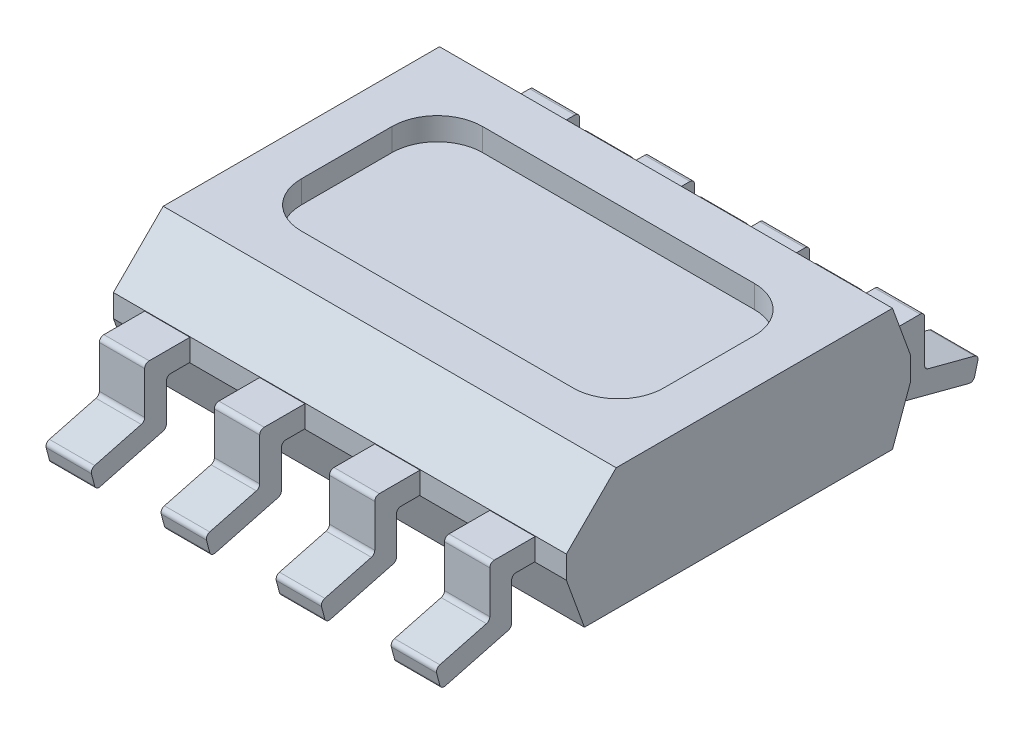
SolidWorks part; units mm, degrees
ref_plane "Front Plane" through (0, 0, 0) normal (0, 0, 1) x (1, 0, 0)
ref_plane "Top Plane" through (0, 0, 0) normal (0, 1, 0) x (1, 0, 0)
ref_plane "Right Plane" through (0, 0, 0) normal (1, 0, 0) x (0, 0, -1)
sketch "Sketch1" plane through (0, 0, 0) normal (0, 1, 0) x (1, 0, 0)
  line L1 (0, 0) -> (5, 0)
  line L2 (0, 0) -> (0, 3.8)
  line L3 (0, 3.8) -> (5, 3.8)
  line L4 (5, 0) -> (5, 3.8)
  dimension "D1" = 5
  dimension "D2" = 3.8
extrude "Boss-Extrude1" add sketch "Sketch1" along normal blind 1.35
sketch "Sketch2" plane through (5, 0, 0) normal (1, 0, 0) x (0, 0, -1)
  line L0 (0.55, 1.35) -> (0, 0.8)
  line L1 (0, 1.35) -> (3.8, 1.35) construction
  line L2 (0, 1.35) -> (0, 0) construction
  line L3 (0, 0.8) -> (0, 0.55)
  line L4 (0, 0.55) -> (0.2, 0)
  line L5 (0, 0) -> (3.8, 0) construction
  line L6 (0.2, 0) -> (3.6, 0)
  line L7 (3.6, 0) -> (3.8, 0.55)
  line L8 (3.8, 1.35) -> (3.8, 0) construction
  line L9 (3.8, 0.55) -> (3.8, 0.8)
  line L10 (3.8, 0.8) -> (3.6, 1.35)
  line L11 (3.6, 1.35) -> (0.55, 1.35)
  line M9 (0, 0) -> (3.8, 0)
  line M10 (3.8, 0) -> (3.8, 1.35)
  line M11 (3.8, 1.35) -> (0, 1.35)
  line M12 (0, 1.35) -> (0, 0)
  dimension "D1" = 0.55
  dimension "D2" = 0.25
  dimension "D3" = 0.25
  dimension "D4" = 0.55
  dimension "D5" = 0.55
  dimension "D6" = 0.55
  dimension "D7" = 0.2
  dimension "D8" = 0.2
  dimension "D9" = 0.2
extrude "Cut-Extrude1" cut sketch "Sketch2" against normal blind 5 contours L0 M11 M12 | L4 M12 M9 | L7 M9 M10 | L10 M10 M11 region at (5, 1.1667, -0.1833) region at (5, 1.1667, -3.7333) region at (5, 0.1833, -0.0667) region at (5, 0.1833, -3.7333)
sketch "Sketch3" plane through (0, 1.35, 0) normal (0, 1, 0) x (1, 0, 0)
  line L0 (0, 3.6) -> (0, 0.55) construction
  line L1 (1, 3.075) -> (4, 3.075)
  line L2 (0.5, 2.575) -> (0.5, 1.575)
  line L3 (1, 1.075) -> (4, 1.075)
  line L4 (4.5, 2.575) -> (4.5, 1.575)
  line L5 (0, 3.6) -> (5, 3.6) construction
  line L7 (0, 0.55) -> (5, 0.55) construction
  arc A0 (0.5, 1.575) -> (1, 1.075) centre (1, 1.575) ccw
  arc A1 (4, 1.075) -> (4.5, 1.575) centre (4, 1.575) ccw
  arc A2 (4, 3.075) -> (4.5, 2.575) centre (4, 2.575) cw
  arc A3 (0.5, 2.575) -> (1, 3.075) centre (1, 2.575) cw
  point P14 (4.5, 1.075)
  point P17 (4.5, 3.075)
  point P20 (0.5, 3.075)
  dimension "D6" = 0.5
  dimension "D1" = 4
  dimension "D2" = 2
  dimension "D3" = 0.5
  dimension "D4" = 0.525
  dimension "D5" = 0.525
extrude "Cut-Extrude2" cut sketch "Sketch3" against normal blind 0.25
ref_plane "Plane1" through (4.405, 0, 0) normal (1, 0, 0) x (0, 0, -1)
sketch "Sketch4" plane through (4.405, 0, 0) normal (1, 0, 0) x (0, 0, -1)
  line L0 (3.8, 0.795) -> (4.25, 0.795)
  line L1 (3.8, 0.8) -> (3.8, 0.55) construction
  line L2 (4.3, 0.745) -> (4.3, 0.2786)
  line L3 (4.3373, 0.2302) -> (4.8516, 0.0948)
  line L4 (4.8873, 0.0337) -> (4.8516, -0.1016)
  line L5 (4.7906, -0.1373) -> (4.0973, 0.0452)
  line L6 (4.06, 0.0935) -> (4.06, 0.505)
  line L7 (4.01, 0.555) -> (3.8, 0.555)
  line L8 (3.8, 0.555) -> (3.8, 0.795)
  arc A0 (4.8516, -0.1016) -> (4.7906, -0.1373) centre (4.8033, -0.0889) cw
  arc A1 (4.8516, 0.0948) -> (4.8873, 0.0337) centre (4.8389, 0.0465) cw
  arc A2 (4.0973, 0.0452) -> (4.06, 0.0935) centre (4.11, 0.0935) cw
  arc A3 (4.3, 0.2786) -> (4.3373, 0.2302) centre (4.35, 0.2786) ccw
  arc A4 (4.06, 0.505) -> (4.01, 0.555) centre (4.01, 0.505) ccw
  arc A5 (4.25, 0.795) -> (4.3, 0.745) centre (4.25, 0.745) cw
  point P17 (4.8389, -0.15)
  point P20 (4.9, 0.0821)
  point P23 (4.06, 0.055)
  point P28 (4.06, 0.555)
  point P31 (4.3, 0.795)
  dimension "D9" = 0.05
  dimension "D1" = 1.1
  dimension "D2" = 0.15
  dimension "D3" = 0.24
  dimension "D4" = 0.24
  dimension "D5" = 0.24
  dimension "D6" = 0.005
  dimension "D7" = 0.5
  dimension "D8" = 0.5
extrude "Boss-Extrude2" add sketch "Sketch4" along normal mid plane 0.5
pattern_linear "LPattern1" count 4 spacing 1.27 along (-1, 0, 0) of "Boss-Extrude2"
ref_plane "Plane2" through (0, 0, -2.075) normal (0, 0, -1) x (-1, 0, 0)
sketch "Sketch6" plane through (5, 0, 0) normal (1, 0, 0) x (0, 0, -1)
  line L0 (0, 0.8) -> (3.8, 0.8) construction
  line L1 (3.8, 0.8) -> (3.8, 0.55) construction
  line L2 (3.8, 0.55) -> (0, 0.55) construction
  line L3 (1.9, 0.8) -> (1.9, 0.55)
sketch "Sketch7" plane through (0, 0, 0) normal (-1, 0, 0) x (0, 0, 1)
  line L0 (-3.8, 0.8) -> (0, 0.8) construction
  line L1 (-1.9, 0.8) -> (-1.9, 0.675)
  line L2 (-1.9, 0.8) -> (-1.9, 0.55) construction
  line L3 (-1.9, 0.675) -> (-2.2759, 0.675)
  line L4 (-2.2759, 0.675) -> (-3.8, 1.4846)
ref_plane "Plane3" through (0, 0, -1.9) normal (0, 0, -1) x (-1, 0, 0)
mirror "Mirror1" about plane through (0, 0, -1.9) normal (0, 0, -1) of "Boss-Extrude2", "LPattern1"
